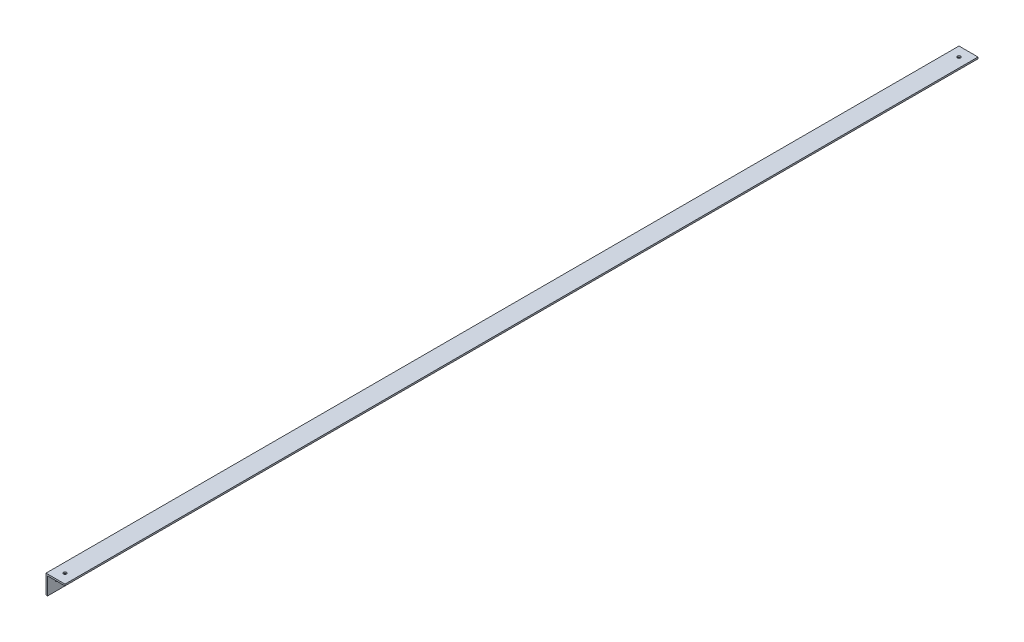
SolidWorks part; units mm, degrees
material "1060 Alloy"
ref_plane "Front Plane" through (0, 0, 0) normal (0, 0, 1) x (1, 0, 0)
ref_plane "Top Plane" through (0, 0, 0) normal (0, 1, 0) x (1, 0, 0)
ref_plane "Right Plane" through (0, 0, 0) normal (1, 0, 0) x (0, 0, -1)
sketch "Sketch1" plane through (0, 0, 0) normal (0, 0, 1) x (1, 0, 0)
  line L0 (0, 0) -> (0, 19.05)
  line L1 (0, 0) -> (19.05, 0)
  line L2 (0, 19.05) -> (1.5875, 19.05)
  line L3 (19.05, 0) -> (19.05, 1.5875)
  line L4 (19.05, 1.5875) -> (1.5875, 1.5875)
  line L5 (1.5875, 1.5875) -> (1.5875, 19.05)
  dimension "D1" = 19.05
  dimension "D2" = 19.05
  dimension "D3" = 1.5875
  dimension "D4" = 1.5875
extrude "Boss-Extrude1" add sketch "Sketch1" against normal blind 914.4
ref_axis "Axis1" through (0, 0, 0) along (0.7071, 0.7071, 0)
ref_plane "Plane1" through (0, 0, 0) normal (-0.7071, 0.7071, 0) x (0.7071, 0.7071, 0)
sketch "Sketch2" plane through (0, 1.5875, 0) normal (0, 1, 0) x (1, 0, 0)
  line L0 (1.5875, 914.4) -> (19.05, 914.4) construction
  line L1 (19.05, 0) -> (1.5875, 0) construction
  line L4 (9.525, -1000) -> (9.525, 49000) construction
  line L5 (1.5875, 0) -> (9.525, 0)
  circle A0 centre (9.525, 9.525) radius 1.5875
  circle A2 centre (9.525, 904.875) radius 1.5875
  dimension "D1" = 9.525
  dimension "D2" = 3.175
  dimension "D3" = 9.525
  dimension "D4" = 3.175
  dimension "D9" = 7.9375
extrude "Cut-Extrude2" cut sketch "Sketch2" against normal blind 2.794 contours A0 | A2
sketch "Sketch4" plane through (1.5875, 0, 0) normal (1, 0, 0) x (0, 0, -1)
  line L0 (914.4, 1.5875) -> (914.4, 9.525)
  line L1 (0, 19.05) -> (0, 0) construction
  line L2 (904.875, 9.525) -> (752.475, 9.525) construction
  line L3 (914.4, 9.525) -> (904.875, 9.525) construction
  line L5 (914.4, 1.5875) -> (914.4, 19.05) construction
  line L6 (0, 1.5875) -> (0, 19.05) construction
  circle A0 centre (9.525, 9.525) radius 1.5875
  circle A2 centre (904.875, 9.525) radius 1.5875
  circle A3 centre (254, 9.525) radius 3.175
  circle A4 centre (285.75, 9.525) radius 3.175
  circle A5 centre (317.5, 9.525) radius 3.175
  circle A6 centre (349.25, 9.525) radius 3.175
  circle A7 centre (469.9, 9.525) radius 3.175
  circle A8 centre (406.4, 9.525) radius 3.175
  circle A9 centre (438.15, 9.525) radius 3.175
  circle A10 centre (374.65, 9.525) radius 3.175
  dimension "D1" = 9.525
  dimension "D2" = 3.175
  dimension "D3" = 7.9375
  dimension "D4" = 3.175
  dimension "D8" = 31.75
  dimension "D6" = 6.35
  dimension "D10" = 120.65
  dimension "D11" = 31.75
  dimension "D12" = 31.75
  dimension "D13" = 31.75
  dimension "D14" = 254
  dimension "D5" = 9.525
  dimension "D7" = 31.75
  dimension "D9" = 31.75
extrude "Cut-Extrude3" cut sketch "Sketch4" against normal blind 8.89 contours A2 | A0 | A3 | A4 | A5 | A6 | A10 | A8 | A9 | A7
mirror "Mirror1" about plane through (0, 19.05, -914.4) normal (0, 1, 0) of "Cut-Extrude3", "Cut-Extrude2", "Boss-Extrude1"
ref_plane "Plane2" through (0, 19.05, 0) normal (0, -1, 0) x (-1, 0, 0)
sketch "Sketch10" plane through (0, 19.05, 0) normal (0, -1, 0) x (-1, 0, 0)
  line L1 (0, 914.4) -> (-19.05, 914.4)
  line L2 (0, 914.4) -> (0, 0)
  line L3 (0, 0) -> (-19.05, 0)
  line L4 (-19.05, 914.4) -> (-19.05, 0)
extrude "Cut-Extrude4" cut sketch "Sketch10" along normal through all
sketch "Sketch11" plane through (0, 0, 0) normal (-1, 0, 0) x (0, 0, 1)
  circle A3 centre (-495.3, 28.575) radius 3.175
  circle A4 centre (-228.6, 28.575) radius 3.175
extrude "Cut-Extrude5" cut sketch "Sketch11" against normal up to next
